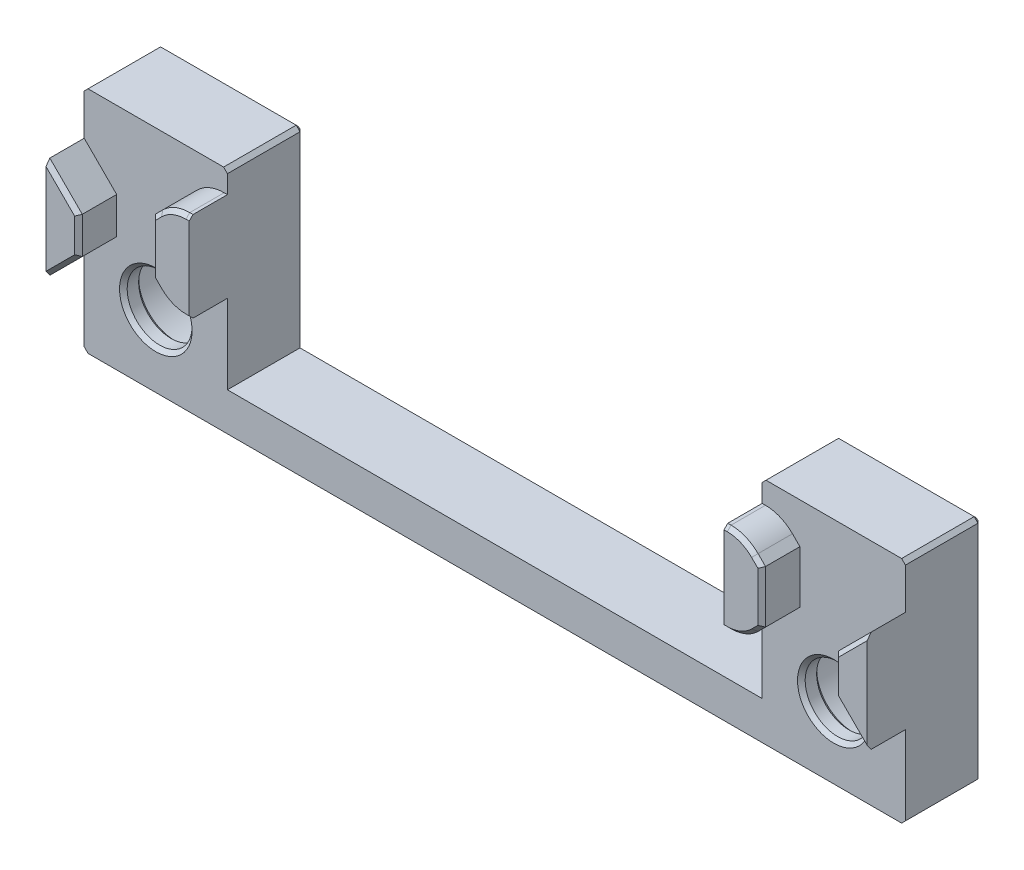
SolidWorks part; units mm, degrees
ref_plane "Front" through (0, 0, 0) normal (0, 0, 1) x (1, 0, 0)
ref_plane "Top" through (0, 0, 0) normal (0, 1, 0) x (1, 0, 0)
ref_plane "Right" through (0, 0, 0) normal (1, 0, 0) x (0, 0, -1)
sketch "Sketch1" plane through (0, 0, 0) normal (0, 0, 1) x (1, 0, 0)
  line L0 (-21.3, -6) -> (21.3, -6)
  line L5 (21.5, -5.8) -> (21.5, 5.8)
  line L6 (21.3, 6) -> (14.2, 6)
  line L7 (14, 5.8) -> (14, -4)
  line L8 (14, -4) -> (-14, -4)
  line L9 (-14, -4) -> (-14, 5.8)
  line L10 (-14.2, 6) -> (-21.3, 6)
  line L11 (-21.5, 5.8) -> (-21.5, -5.8)
  line L12 (21.5, 5.8) -> (21.5, -5.8) construction
  line L13 (21.3, 6) -> (14, 6) construction
  line L14 (21.3, -6) -> (-21.3, -6) construction
  line L15 (21.5, 5.8) -> (21.3, 6)
  line L16 (-14, 6) -> (-21.3, 6) construction
  line L17 (-21.5, 5.8) -> (-21.5, -5.8) construction
  line L18 (14.2, 6) -> (14, 5.8)
  line L19 (21.3, -6) -> (21.5, -5.8)
  line L20 (-21.5, -5.8) -> (-21.3, -6)
  line L21 (-21.3, 6) -> (-21.5, 5.8)
  line L22 (-14, 5.8) -> (-14.2, 6)
  point P0 (-21.5, -6)
  point P1 (21.5, -6)
  point P2 (21.5, 6)
  point P4 (14, 6)
  point P6 (-21.5, 6)
  point P13 (-14, 6)
  dimension "D1" = 45
  dimension "D3" = 45
  dimension "D6" = 0.2
  dimension "D5" = 45
  dimension "D7" = 45
  dimension "D12" = 0.2
  dimension "D8" = 45
  dimension "D11" = 0.2
  dimension "D9" = 0.2
  dimension "D10" = 45
  dimension "D2" = 0.2
  dimension "D4" = 0.2
extrude "Boss-Extrude1" add sketch "Sketch1" against normal blind 4
sketch "Sketch3" plane through (0, 0, 0) normal (0, 0, 1) x (1, 0, 0)
  line L12 (14, 4.85) -> (14, 0.15)
  line L13 (14, 5.8) -> (14, -4) construction
  line L20 (15.975, 1.125) -> (15.975, 3.875)
  line L24 (15.975, 3.875) -> (15.5858, 4.2642)
  line L26 (14.1716, 4.85) -> (13.3284, 4.85)
  line L28 (11.9142, 4.2642) -> (11.5, 3.85)
  line L30 (11.5, 3.85) -> (11.5, 1.15)
  line L32 (11.5, 1.15) -> (11.9142, 0.7358)
  line L36 (13.3284, 0.15) -> (14.1716, 0.15)
  line L37 (15.5858, 0.7358) -> (15.975, 1.125)
  line L38 (15.975, 1.125) -> (15.975, 3.875)
  line L39 (15.975, 3.875) -> (15.5858, 4.2642)
  line L40 (14.1716, 4.85) -> (13.3284, 4.85)
  line L41 (11.9142, 4.2642) -> (11.5, 3.85)
  line L42 (11.5, 3.85) -> (11.5, 1.15)
  line L43 (11.5, 1.15) -> (11.9142, 0.7358)
  line L44 (13.3284, 0.15) -> (14.1716, 0.15)
  line L45 (15.5858, 0.7358) -> (15.975, 1.125)
  arc A10 (15.5858, 4.2642) -> (14.1716, 4.85) centre (14.1716, 2.85) ccw
  arc A11 (13.3284, 4.85) -> (11.9142, 4.2642) centre (13.3284, 2.85) ccw
  arc A12 (11.9142, 0.7358) -> (13.3284, 0.15) centre (13.3284, 2.15) ccw
  arc A13 (14.1716, 0.15) -> (15.5858, 0.7358) centre (14.1716, 2.15) ccw
  arc A14 (15.5858, 4.2642) -> (14.1716, 4.85) centre (14.1716, 2.85) ccw
  arc A15 (13.3284, 4.85) -> (11.9142, 4.2642) centre (13.3284, 2.85) ccw
  arc A16 (11.9142, 0.7358) -> (13.3284, 0.15) centre (13.3284, 2.15) ccw
  arc A17 (14.1716, 0.15) -> (15.5858, 0.7358) centre (14.1716, 2.15) ccw
  dimension "D1" = 0
extrude "Slot Aligner" add sketch "Sketch3" along normal blind 2 contours L44 A17 L45 L38 L39 A14 L40 A15 L12 A16 region at (14.9111, 2.5, 0)
mirror "Mirror3" about plane through (0, 0, 0) normal (1, 0, 0) of "Slot Aligner"
sketch "Sketch4" plane through (0, 0, 0) normal (0, 0, 1) x (1, 0, 0)
  line L4 (21.4, 3.5586) -> (21.5, 3.6586)
  line L5 (21.5, 3.8) -> (21.5, -1.8) construction
  line L6 (21.5, 3.6586) -> (21.5, -1.6586)
  line L7 (21.5, -1.6586) -> (21.4, -1.5586)
  line L8 (21.4, -1.5586) -> (21.4, 3.5586)
  line L9 (21.4, 3.5586) -> (19.8, 1.9586)
  line L10 (19.8, 1.9586) -> (19.8, 0.0414)
  line L11 (19.8, 0.0414) -> (21.4, -1.5586)
  line L12 (21.4, -1.5586) -> (21.4, 3.5586) construction
  line L13 (21.4, 3.5586) -> (19.8, 1.9586)
  line L14 (19.8, 1.9586) -> (19.8, 0.0414)
  line L15 (19.8, 0.0414) -> (21.4, -1.5586)
  dimension "D1" = 0.1
extrude "Aligner" add sketch "Sketch4" along normal blind 2
mirror "Aligners" about plane through (0, 0, 0) normal (1, 0, 0) of "Aligner"
chamfer "Deburs" distance 0.2 angle 45 34 edges at (14, 0.9, -4) (14.1, 5.9, -4) (17.75, 6, -4) (21.4, 5.9, -4) (21.5, 0, -4) (21.4, -5.9, -4) (0, -6, -4) (-21.4, -5.9, -4) (-21.5, 0, -4) (-21.4, 5.9, -4) (-17.75, 6, -4) (-14.1, 5.9, -4) (-14, 0.9, -4) (0, -4, -4) (-20.65, 2.8086, 2) (-20.65, -0.8086, 2) (-19.8, 1, 2) (20.65, -0.8086, 2) (19.8, 1, 2) (20.65, 2.8086, 2) (-14.0858, 4.85, 2) (-14.0858, 0.15, 2) (-14.9369, 4.6978, 2) (-14.9369, 0.3022, 2) (-15.7804, 4.0696, 2) (-15.7804, 0.9304, 2) (-15.975, 2.5, 2) (14.0858, 4.85, 2) (14.0858, 0.15, 2) (14.9369, 4.6978, 2) (14.9369, 0.3022, 2) (15.7804, 4.0696, 2) (15.975, 2.5, 2) (15.7804, 0.9304, 2)
sketch "Sketch5" plane through (0, 0, -4) normal (0, 0, -1) x (-1, 0, 0)
  point P0 (-17.75, -2.25)
  point P1 (17.75, -2.25)
hole_wizard "CBORE for M3 SHCS1" positions "Sketch5" profile "Sketch6" counterbore size "M3" standard "ANSI Metric" end condition through all
sketch "Sketch6" plane through (17.75, -2.25, -4) normal (1, 0, 0) x (0, 1, 0)
  line L0 (0, 0) -> (0, 6)
  line L1 (0, 6) -> (1.7, 6)
  line L3 (1.7, 6) -> (1.7, 3)
  line L4 (1.7, 3) -> (3.25, 3)
  line L5 (3.25, 3) -> (3.25, 0)
  line L7 (3.25, 0) -> (0, 0)
  line L11 (0, -6.35) -> (0, 107.95) construction
  dimension "Thru Hole Dia." = 3.4
  dimension "Thru Hole Depth" = 6
  dimension "C'Bore Dia." = 6.5
  dimension "C'Bore Depth" = 3
chamfer "Chamfer1" distance 0.2 angle 45 6 edges at (-19.45, -2.25, 0) (-19.45, -2.25, -1) (16.05, -2.25, 0) (16.05, -2.25, -1) (14.5, -2.25, -4) (-21, -2.25, -4)
